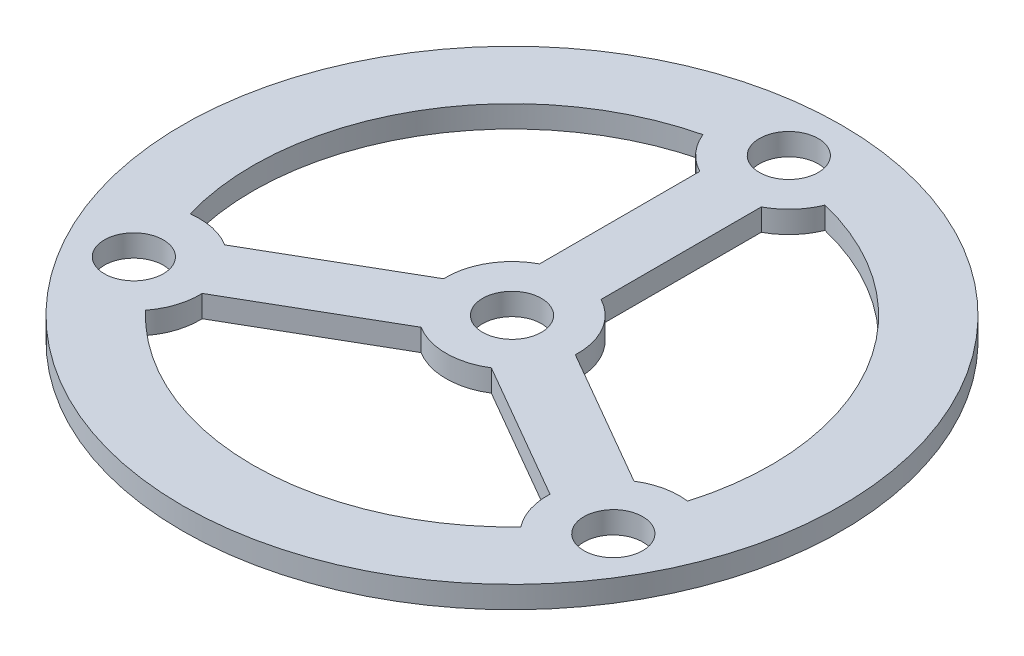
SolidWorks part; units mm, degrees
ref_plane "Front Plane" through (0, 0, 0) normal (0, 0, 1) x (1, 0, 0)
ref_plane "Top Plane" through (0, 0, 0) normal (0, 1, 0) x (1, 0, 0)
ref_plane "Right Plane" through (0, 0, 0) normal (1, 0, 0) x (0, 0, -1)
sketch "Sketch1" plane through (0, 0, 0) normal (0, 1, 0) x (1, 0, 0)
  circle A0 centre (0, 0) radius 37.5
  arc A1 (-6.9458, 28.6706) -> (-28.3024, -8.32) centre (0, 0) ccw
  arc A2 (-6.9458, 28.6706) -> (6.9458, 28.6706) centre (0, 31.5) ccw
  circle A3 centre (0, 31.5) radius 3.35
  arc A4 (28.3024, -8.32) -> (21.3566, -20.3506) centre (27.2798, -15.75) ccw
  circle A5 centre (27.2798, -15.75) radius 3.35
  arc A6 (-21.3566, -20.3506) -> (-28.3024, -8.32) centre (-27.2798, -15.75) ccw
  circle A7 centre (-27.2798, -15.75) radius 3.35
  arc A8 (28.3024, -8.32) -> (6.9458, 28.6706) centre (0, 0) ccw
  arc A9 (-21.3566, -20.3506) -> (21.3566, -20.3506) centre (0, 0) ccw
  point P18 (0, 0)
  dimension "D1" = 75
  dimension "D2" = 8
  dimension "D3" = 6.7
  dimension "D4" = 15
  dimension "D5" = 31.5
  dimension "D6" = 3
extrude "Boss-Extrude1" add sketch "Sketch1" along normal blind 2.5
sketch "Sketch2" plane through (0, 0, 0) normal (0, 1, 0) x (1, 0, 0)
  line L0 (3.5, 6.6332) -> (3.5, 31.5)
  line L1 (-7.4946, -0.2855) -> (-29.0298, -12.7189)
  line L2 (-3.9946, -6.3477) -> (-25.5298, -18.7811)
  line L3 (-1.75, 3.0311) -> (-1.675, 2.9012)
  line L4 (-29.0298, -12.7189) -> (-28.9548, -12.8488)
  line L5 (-25.6048, -18.6512) -> (-25.5298, -18.7811)
  line L6 (1.675, -2.9012) -> (1.75, -3.0311)
  line L7 (-3.5, 6.6332) -> (-3.5, 31.5)
  line L8 (3.5, 31.5) -> (3.35, 31.5)
  line L9 (-3.35, 31.5) -> (-3.5, 31.5)
  line L10 (3.9946, -6.3477) -> (25.5298, -18.7811)
  line L11 (7.4946, -0.2855) -> (29.0298, -12.7189)
  line L12 (25.5298, -18.7811) -> (25.6048, -18.6512)
  line L13 (28.9548, -12.8488) -> (29.0298, -12.7189)
  circle A0 centre (0, 0) radius 7.5
  circle A1 centre (0, 0) radius 3.35
  arc A2 (-3.35, 31.5) -> (3.35, 31.5) centre (0, 31.5) ccw
  arc A3 (-25.6048, -18.6512) -> (-28.9548, -12.8488) centre (-27.2798, -15.75) ccw
  arc A4 (28.9548, -12.8488) -> (25.6048, -18.6512) centre (27.2798, -15.75) ccw
  point P32 (0, 0)
  point P34 (0, 0)
  dimension "D1" = 6.7
  dimension "D2" = 15
  dimension "D3" = 0.1299
  dimension "D4" = 3
extrude "Boss-Extrude2" add sketch "Sketch2" along normal blind 2.5 contours A4 L13 L11 A0 L10 L12 | A0 A1 | A3 L5 L2 A0 L1 L4 | A2 L9 L7 A0 L0 L8 region at (0, 0, -18.1172) region at (6.241, 0, -3.7634) region at (15.69, 0, 9.0586) region at (-15.69, 0, 9.0586)
